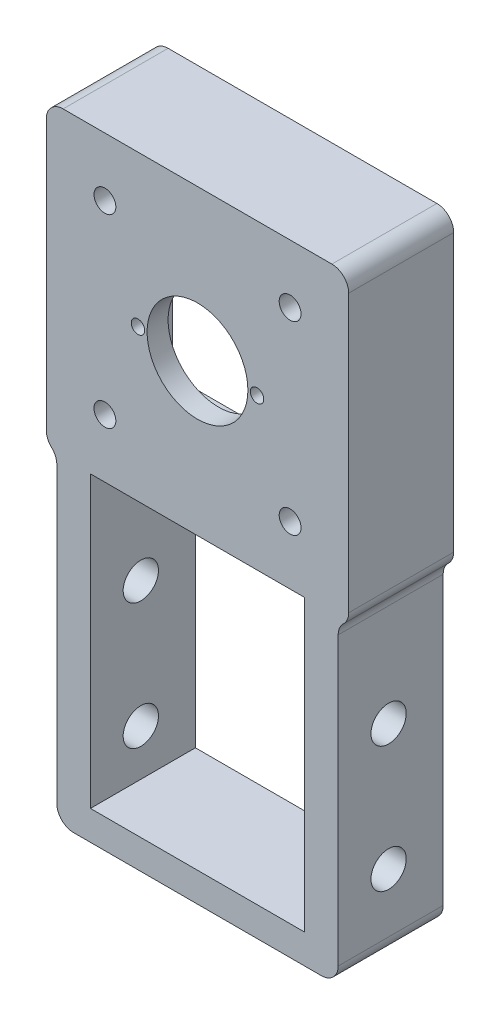
SolidWorks part; units mm, degrees
ref_plane "Front Plane" through (0, 0, 0) normal (0, 0, 1) x (1, 0, 0)
ref_plane "Top Plane" through (0, 0, 0) normal (0, 1, 0) x (1, 0, 0)
ref_plane "Right Plane" through (0, 0, 0) normal (1, 0, 0) x (0, 0, -1)
sketch "Sketch1" plane through (0, 0, 0) normal (0, 0, 1) x (1, 0, 0)
  line L0 (0, 0) -> (-39.37, 0)
  line L1 (-39.37, 0) -> (-39.37, 39.37)
  line L2 (-39.37, 39.37) -> (0, 39.37)
  line L3 (0, 39.37) -> (0, 0)
  line L4 (-33.6855, 0) -> (-33.6855, 5.6845)
  line L5 (-33.6855, 5.6845) -> (-39.37, 5.6845)
  line L6 (-39.37, 19.685) -> (0, 19.685) construction
  line L7 (-19.685, 39.37) -> (-19.685, 0) construction
  circle A0 centre (-33.6855, 5.6845) radius 1.651
  circle A1 centre (-33.6855, 33.6855) radius 1.651
  circle A2 centre (-5.6845, 5.6845) radius 1.651
  circle A3 centre (-5.6845, 33.6855) radius 1.651
  circle A4 centre (-19.685, 19.685) radius 7.62
  circle A5 centre (-28.6855, 19.685) radius 1.016
  circle A6 centre (-10.6845, 19.685) radius 1.016
  dimension "D5" = 3.302
  dimension "D6" = 15.24
  dimension "D7" = 2.032
  dimension "D1" = 39.37
  dimension "D2" = 39.37
  dimension "D3" = 5.6845
  dimension "D4" = 5.6845
  dimension "D8" = 10.6845
extrude "Boss-Extrude1" add sketch "Sketch1" along normal blind 3.175 contours A0 L4 L0 L3 L2 L1 L5 A4 A3 A1 A2 | A0 L5 L1 L0 L4 region at (-16.8427, 0.5568, 0) region at (-36.6797, 2.6903, 0)
sketch "Sketch3" plane through (0, 0, 0) normal (0, 0, -1) x (-1, 0, 0)
  line L0 (0, 0) -> (39.37, 0) construction
  line L1 (39.37, 0) -> (39.37, 39.37) construction
  line L2 (0, 39.37) -> (0, 0) construction
  line L3 (39.37, 39.37) -> (0, 39.37) construction
  line L4 (0, 0) -> (39.37, 0)
  line L5 (39.37, 0) -> (39.37, 39.37)
  line L6 (0, 39.37) -> (0, 0)
  line L7 (39.37, 39.37) -> (0, 39.37)
  line L8 (-3.175, -3.175) -> (42.545, -3.175)
  line L9 (42.545, -3.175) -> (42.545, 42.545)
  line L10 (42.545, 42.545) -> (-3.175, 42.545)
  line L11 (-3.175, 42.545) -> (-3.175, -3.175)
  dimension "D1" = 3.175
extrude "Boss-Extrude2" add sketch "Sketch3" along normal blind 12.7 and the other way blind 3.175
sketch "Sketch5" plane through (0, -3.175, 0) normal (0, -1, 0) x (-1, 0, 0)
  line L0 (35.8775, -3.175) -> (35.8775, 12.7)
  line L1 (-3.175, -3.175) -> (42.545, -3.175) construction
  line L2 (-3.175, 12.7) -> (42.545, 12.7) construction
  line L3 (19.685, -3.175) -> (19.685, 12.7) construction
  line L8 (42.545, -3.175) -> (42.545, 12.7)
  line L9 (42.545, 12.7) -> (-3.175, 12.7)
  line L10 (-3.175, 12.7) -> (-3.175, -3.175)
  line L11 (-3.175, -3.175) -> (42.545, -3.175)
  line L12 (40.9575, -3.175) -> (40.9575, 12.7)
  line L13 (40.9575, 12.7) -> (35.8775, 12.7)
  line L15 (35.8775, -3.175) -> (40.9575, -3.175)
  line L17 (42.545, -3.175) -> (42.545, 12.7) construction
  line L18 (3.4925, -3.175) -> (-1.5875, -3.175)
  line L19 (-1.5875, 12.7) -> (3.4925, 12.7)
  line L20 (-1.5875, -3.175) -> (-1.5875, 12.7)
  line L21 (3.4925, -3.175) -> (3.4925, 12.7)
  point P8 (0, 0)
  point P9 (0, 0)
  point P11 (0, 0)
  point P13 (0, 0)
  dimension "D1" = 1.5875
  dimension "D3" = 5.08
  dimension "D2" = 0
extrude "Boss-Extrude3" add sketch "Sketch5" along normal blind 48.26 contours L12 L13 L0 L15 | L18 L20 L19 L21
ref_plane "Plane1" through (-35.8775, -51.435, -12.7) normal (0, 1, 0) x (1, 0, 0)
sketch "Sketch6" plane through (-35.8775, -51.435, -12.7) normal (0, 1, 0) x (1, 0, 0)
  line L0 (37.465, -15.875) -> (37.465, 0) construction
  line L1 (0, 0) -> (37.465, 0)
  line L2 (-5.08, -15.875) -> (-5.08, 0) construction
  line L3 (-5.08, 0) -> (37.465, 0)
  line L4 (-5.08, 0) -> (-5.08, -15.875)
  line L5 (-5.08, -15.875) -> (37.465, -15.875)
  line L6 (37.465, 0) -> (37.465, -15.875)
  line L8 (0, -15.875) -> (-5.08, -15.875) construction
  point P1 (0, 0)
  point P3 (0, 0)
  point P12 (0, 0)
  point P13 (29.8799, 0)
  point P14 (46.9354, 0)
  point P15 (39.0814, 0)
  point P18 (0, 0)
extrude "Boss-Extrude4" add sketch "Sketch6" along normal blind 4.445 contours L4 L5 L1 L3 region at (-19.685, -51.435, -4.7625)
sketch "Sketch7" plane through (-42.545, 0, 0) normal (-1, 0, 0) x (0, 0, 1)
  line L0 (3.175, -51.435) -> (-12.7, -51.435) construction
  line L1 (3.175, -3.175) -> (3.175, 42.545) construction
  circle A0 centre (-4.445, -40.005) radius 2.667
  circle A1 centre (-4.445, -20.955) radius 2.667
  dimension "D2" = 5.334
  dimension "D1" = 19.05
  dimension "D3" = 11.43
  dimension "D4" = 7.62
extrude "Cut-Extrude1" cut sketch "Sketch7" against normal through all
fillet "Fillet1" radius 2.54 3 edges at (-40.9575, -51.435, -4.7625) (1.5875, -3.175, -4.7625) (1.5875, -51.435, -4.7625)
fillet "Fillet2" radius 2.54 4 edges at (-42.545, -3.175, -4.7625) (3.175, 42.545, -4.7625) (-42.545, 42.545, -4.7625) (3.175, -3.175, -4.7625)
fillet "Fillet3" radius 2.54 1 edges at (-40.9575, -3.175, -4.7625)
